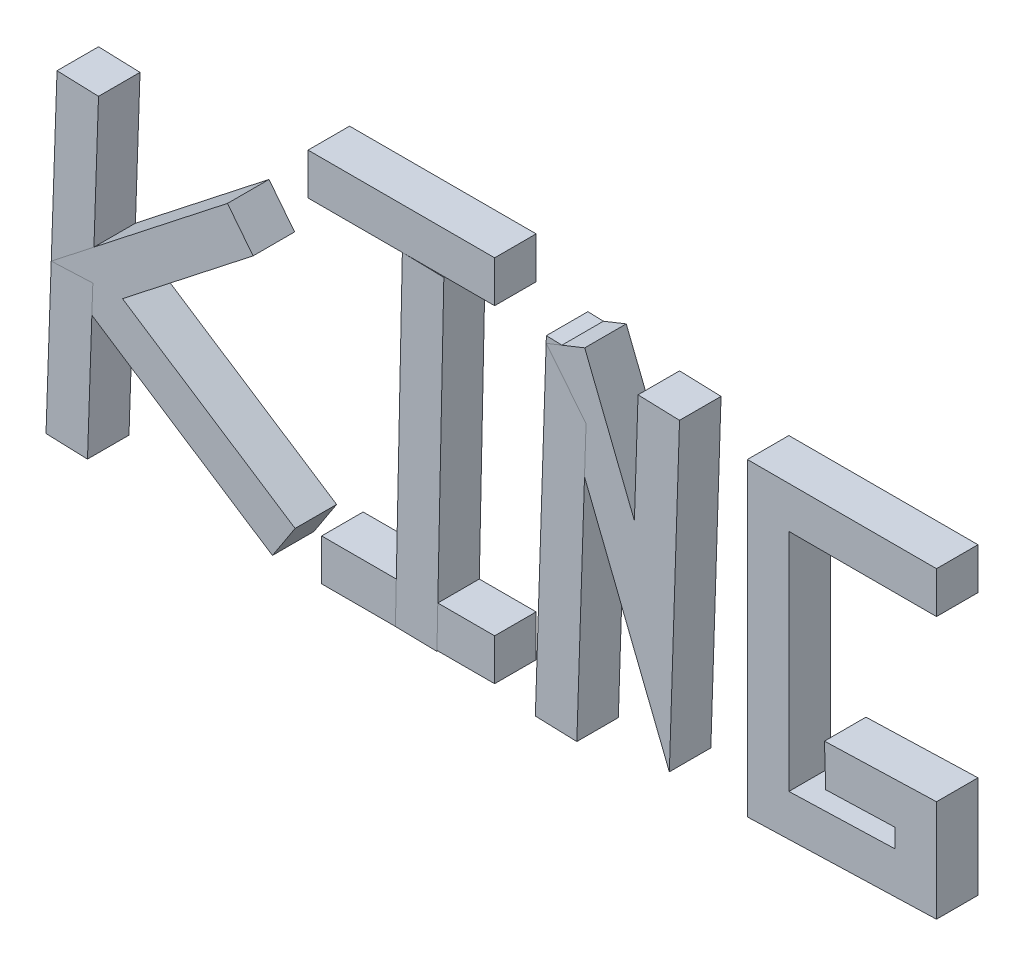
SolidWorks part; units mm, degrees
ref_plane "Front Plane" through (0, 0, 0) normal (0, 0, 1) x (1, 0, 0)
ref_plane "Top Plane" through (0, 0, 0) normal (0, 1, 0) x (1, 0, 0)
ref_plane "Right Plane" through (0, 0, 0) normal (1, 0, 0) x (0, 0, -1)
sketch "Sketch1" plane through (0, 0, 0) normal (0, 0, 1) x (1, 0, 0)
  line L3 (14.0983, 85.8159) -> (11.4421, 8.7859)
  line L4 (12.7042, 45.3868) -> (55.1674, 78.6646)
  line L5 (12.7042, 45.3868) -> (65.9965, 10.6248)
  line L6 (74.5781, 89.4938) -> (119.5293, 89.4938)
  line L7 (97.2927, 89.4938) -> (95.6235, 10.6248)
  line L8 (77.8473, 10.6248) -> (119.5293, 10.6248)
  line L9 (131.9931, 89.4938) -> (129.3369, 8.7859)
  line L10 (131.9393, 87.8592) -> (161.62, 13.281)
  line L11 (161.62, 13.281) -> (164.0745, 87.8592)
  line L12 (225.982, 87.8592) -> (180.4178, 87.8592)
  line L13 (180.4178, 87.8592) -> (180.4178, 13.281)
  line L14 (180.4178, 13.281) -> (225.982, 14.7113)
  line L15 (225.982, 14.7113) -> (225.982, 39.2301)
  line L16 (225.982, 39.2301) -> (198.9865, 38.3828)
extrude "Extrude-Thin16" add sketch "Sketch1" along normal blind 10 thin thin type one direction reverse wall 10
